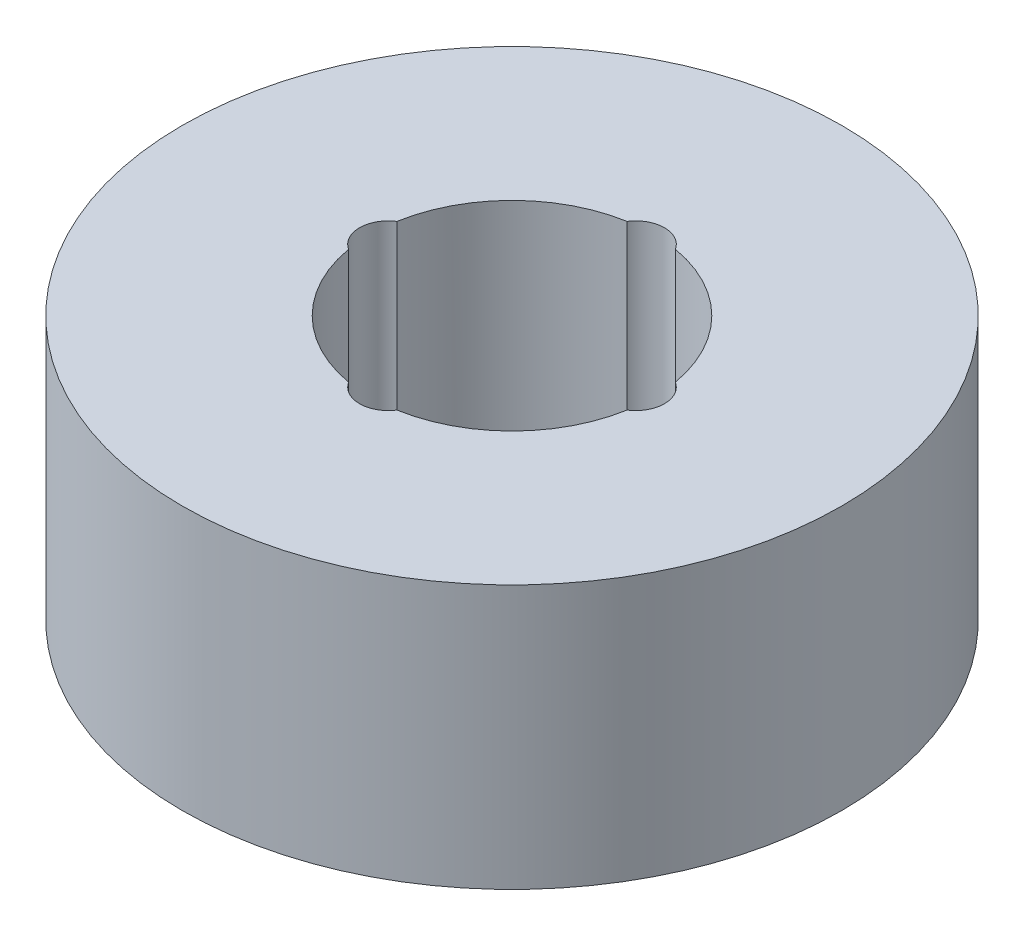
SolidWorks part; units mm, degrees
ref_plane "Front Plane" through (0, 0, 0) normal (0, 0, 1) x (1, 0, 0)
ref_plane "Top Plane" through (0, 0, 0) normal (0, 1, 0) x (1, 0, 0)
ref_plane "Right Plane" through (0, 0, 0) normal (1, 0, 0) x (0, 0, -1)
sketch "Sketch1" plane through (0, 0, 0) normal (0, 1, 0) x (1, 0, 0)
  circle A0 centre (0, 0) radius 17.5
  dimension "FLANGE_OD" = 35
extrude "Boss-Extrude1" add sketch "Sketch1" along normal blind 14
sketch "Sketch2" plane through (0, 0, 0) normal (0, 1, 0) x (1, 0, 0)
  circle A0 centre (0, 0) radius 7.5
  dimension "BORE_D" = 15
extrude "Cut-Extrude1" cut sketch "Sketch2" along normal through all
sketch "Sketch3" plane through (0, 14, 0) normal (0, 1, 0) x (1, 0, 0)
  circle A0 centre (0, 0) radius 6.5674 construction
  circle A1 centre (-6.5674, 0) radius 1.5242
  dimension "BOLT_D" = 3.0485
  dimension "BOLT_PCD" = 13.1347
extrude "Cut-Extrude2" cut sketch "Sketch3" against normal blind 8.9584
pattern_circular "CirPattern1" count 4 over 360 about axis through (0, 0, 0) along (0, 1, 0) of "Cut-Extrude2"
